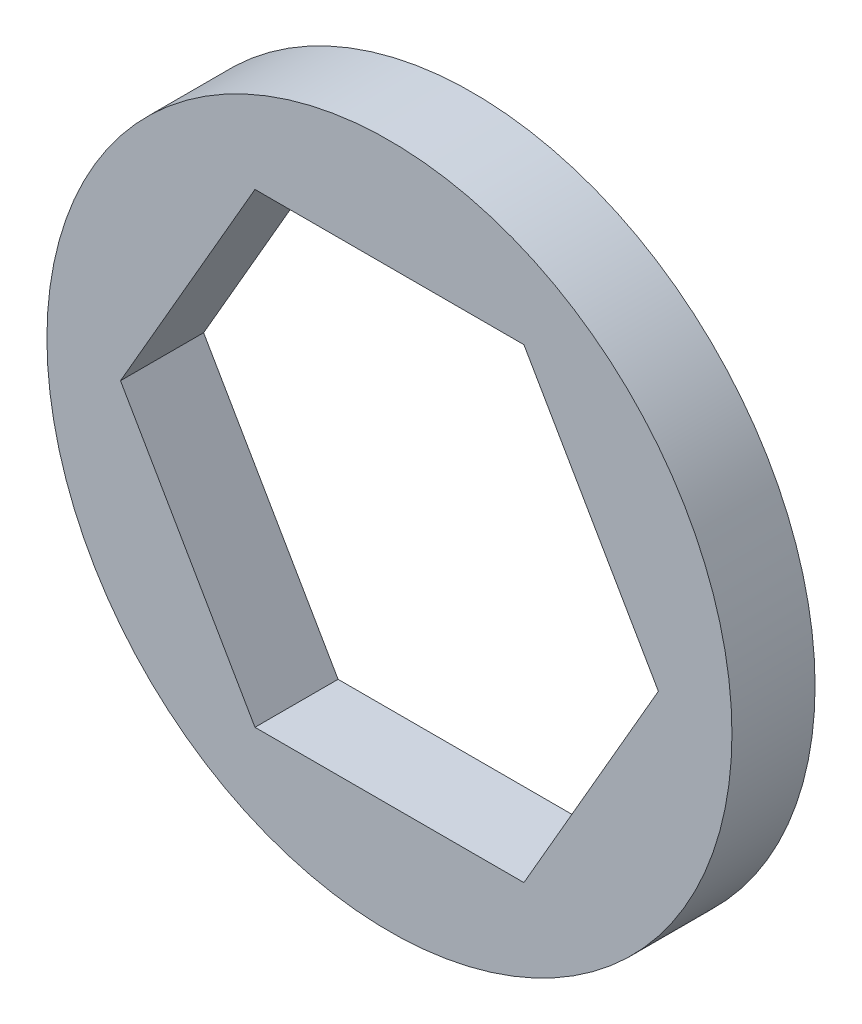
SolidWorks part; units mm, degrees
material "PET"
ref_plane "Front Plane" through (0, 0, 0) normal (0, 0, 1) x (1, 0, 0)
ref_plane "Top Plane" through (0, 0, 0) normal (0, 1, 0) x (1, 0, 0)
ref_plane "Right Plane" through (0, 0, 0) normal (1, 0, 0) x (0, 0, -1)
sketch "Sketch1" plane through (0, 0, 0) normal (0, 0, 1) x (1, 0, 0)
  line L7 (7.479, 0) -> (3.7395, 6.477)
  line L8 (3.7395, 6.477) -> (-3.7395, 6.477)
  line L9 (-3.7395, 6.477) -> (-7.479, 0)
  line L10 (-7.479, 0) -> (-3.7395, -6.477)
  line L11 (-3.7395, -6.477) -> (3.7395, -6.477)
  line L12 (3.7395, -6.477) -> (7.479, 0)
  circle A2 centre (0, 0) radius 6.477 construction
  circle A3 centre (0, 0) radius 9.525
  dimension "D1" = 19.05
  dimension "D2" = 12.954
extrude "Boss-Extrude1" add sketch "Sketch1" along normal mid plane 2.3114
equation "\"D1@Boss-Extrude1\"=((0.307)/2)-(1/16)"
